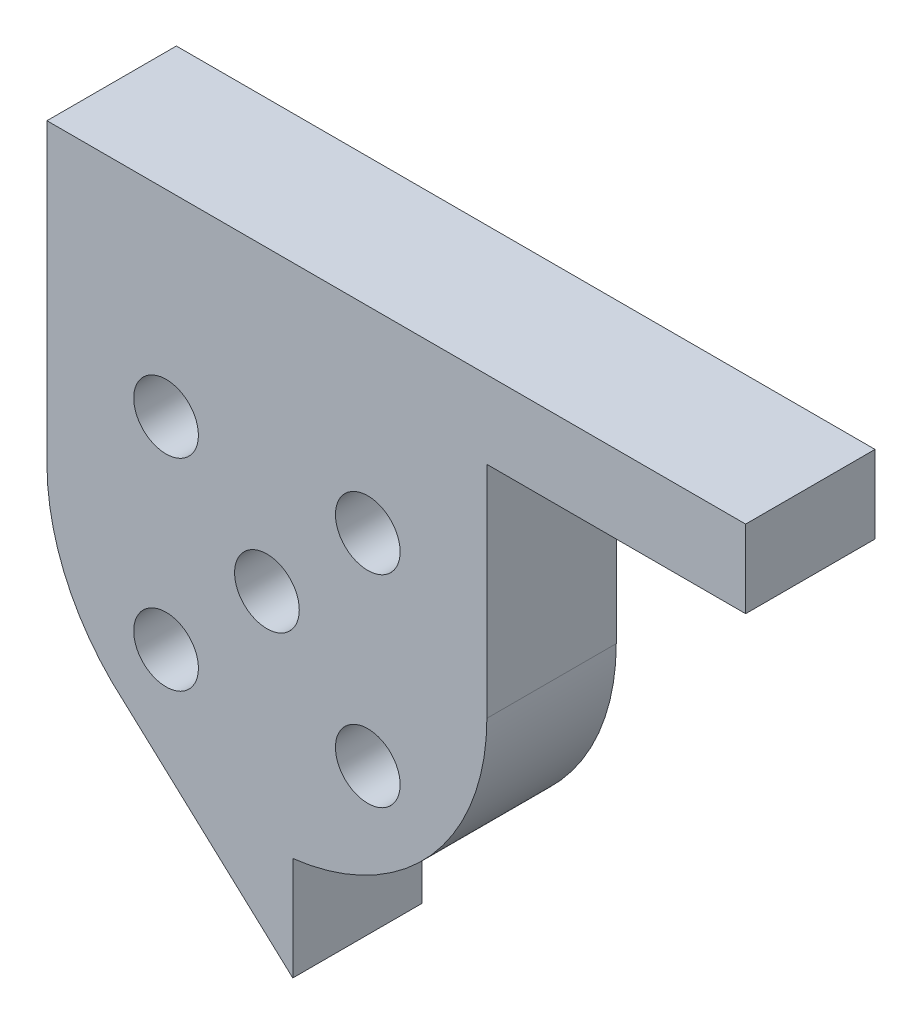
SolidWorks part; units mm, degrees
ref_plane "Front Plane" through (0, 0, 0) normal (0, 0, 1) x (1, 0, 0)
ref_plane "Top Plane" through (0, 0, 0) normal (0, 1, 0) x (1, 0, 0)
ref_plane "Right Plane" through (0, 0, 0) normal (1, 0, 0) x (0, 0, -1)
sketch "Sketch1" plane through (0, 0, 0) normal (0, 0, 1) x (1, 0, 0)
  line L0 (10.795, 0) -> (10.795, 10.795)
  line L1 (-4.95, 4.95) -> (4.95, 4.95) construction
  line L2 (-4.95, 4.95) -> (-4.95, -4.95) construction
  line L3 (-4.95, -4.95) -> (4.95, -4.95) construction
  line L4 (4.95, 4.95) -> (4.95, -4.95) construction
  line L5 (-4.95, 4.95) -> (4.95, -4.95) construction
  line L6 (-4.95, -4.95) -> (4.95, 4.95) construction
  line L7 (10.795, 10.795) -> (23.495, 10.795)
  line L8 (23.495, 10.795) -> (23.495, 14.605)
  line L9 (23.495, 14.605) -> (-10.795, 14.605)
  line L10 (-10.795, 14.605) -> (-10.795, 0)
  line L11 (1.27, -10.72) -> (1.27, -15.8)
  line L12 (1.27, -15.8) -> (-7.62, -7.6464)
  circle A0 centre (0, 0) radius 1.5875
  circle A1 centre (-4.95, 4.95) radius 1.5875
  circle A2 centre (-4.95, -4.95) radius 1.5875
  circle A3 centre (4.95, -4.95) radius 1.5875
  circle A4 centre (4.95, 4.95) radius 1.5875
  arc A5 (-10.795, 0) -> (-7.62, -7.6464) centre (0, 0) ccw
  arc A6 (10.795, 0) -> (-10.795, 0) centre (0, 0) ccw construction
  arc A7 (-7.62, -7.6464) -> (1.27, -10.72) centre (0, 0) ccw construction
  arc A8 (1.27, -10.72) -> (10.795, 0) centre (0, 0) ccw
  point P0 (0, 0)
  dimension "D3" = 3.175
  dimension "D4" = 21.59
  dimension "D1" = 9.9
  dimension "D2" = 9.9
  dimension "D5" = 12.7
  dimension "D6" = 3.81
  dimension "D7" = 1.27
  dimension "D8" = 5.08
  dimension "D9" = 7.62
extrude "Boss-Extrude1" add sketch "Sketch1" along normal blind 6.35
